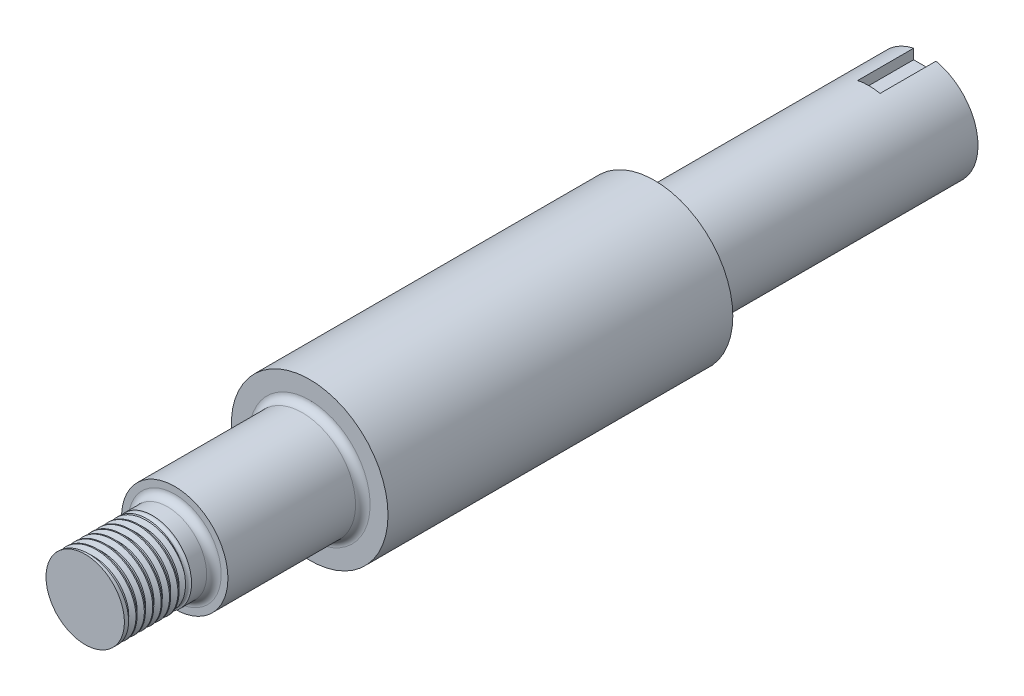
SolidWorks part; units mm, degrees
material "AISI 1020"
ref_plane "Front Plane" through (0, 0, 0) normal (0, 0, 1) x (1, 0, 0)
ref_plane "Top Plane" through (0, 0, 0) normal (0, 1, 0) x (1, 0, 0)
ref_plane "Right Plane" through (0, 0, 0) normal (1, 0, 0) x (0, 0, -1)
sketch "Sketch Spindle Skeleton" plane through (0, 0, 0) normal (1, 0, 0) x (0, 0, -1)
  line L0 (-109.9, -9.5) -> (-134, -9.5)
  line L5 (-1000, 0) -> (49000, 0)
  line L6 (0, -9.5) -> (0, 9.5)
  line L13 (0, 9.5) -> (-48.3, 9.5)
  line L26 (-48.3, 9.5) -> (-48.3, 14)
  line L27 (-48.3, 14) -> (-109.9, 14)
  line L32 (-109.9, 14) -> (-109.9, 9.5)
  line L34 (-150, 7) -> (-150, -7)
  line L36 (-109.9, -9.5) -> (-109.9, -14)
  line L37 (-109.9, -14) -> (-48.3, -14)
  line L38 (-48.3, -14) -> (-48.3, -9.5)
  line L39 (0, -9.5) -> (-48.3, -9.5)
  line L40 (-24.2, 36) -> (-19.2, 36)
  line L41 (-126.5, 22.5) -> (-109.9, 22.5)
  line L42 (-126.5, 22.5) -> (-126.5, -22.5)
  line L43 (-126.5, -22.5) -> (-109.9, -22.5)
  line L44 (-109.9, 22.5) -> (-109.9, -22.5)
  line L45 (-126.5, 22.5) -> (-109.9, -22.5) construction
  line L46 (-126.5, -22.5) -> (-109.9, 22.5) construction
  line L47 (-31.7, 22.5) -> (-48.3, 22.5)
  line L48 (-31.7, 22.5) -> (-31.7, -22.5)
  line L49 (-31.7, -22.5) -> (-48.3, -22.5)
  line L50 (-48.3, 22.5) -> (-48.3, -22.5)
  line L51 (-31.7, 22.5) -> (-48.3, -22.5) construction
  line L52 (-31.7, -22.5) -> (-48.3, 22.5) construction
  line L59 (-19.2, 36) -> (-19.2, -36)
  line L60 (-19.2, -36) -> (-24.2, -36)
  line L61 (-24.2, -22.5) -> (-29.2, -22.5)
  line L62 (-29.2, -22.5) -> (-29.2, -17.5)
  line L63 (-29.2, -17.5) -> (-24.2, -17.5)
  line L64 (-24.2, -17.5) -> (-24.2, 17.5)
  line L65 (-24.2, 17.5) -> (-29.2, 17.5)
  line L66 (-29.2, 17.5) -> (-29.2, 22.5)
  line L67 (-29.2, 22.5) -> (-24.2, 22.5)
  line L68 (-24.2, 22.5) -> (-24.2, 36)
  line L69 (-24.2, -22.5) -> (-24.2, -36)
  line L71 (-131.5, 36) -> (-25.2, 36)
  line L72 (-131.5, 36) -> (-131.5, -36)
  line L73 (-131.5, -36) -> (-25.2, -36)
  line L74 (-25.2, 36) -> (-25.2, -36)
  line L75 (-131.5, 36) -> (-25.2, -36) construction
  line L76 (-131.5, -36) -> (-25.2, 36) construction
  line L77 (-134, -9.5) -> (-134, -7)
  line L78 (-134, -7) -> (-150, -7)
  line L79 (-109.9, 9.5) -> (-134, 9.5)
  line L80 (-134, 7) -> (-150, 7)
  line L81 (-134, 9.5) -> (-134, 7)
  line L82 (-121.95, 9.5) -> (-121.95, -9.5) construction
  line L83 (-24.15, 9.5) -> (-24.15, -9.5) construction
  point P3 (0, 0)
  point P18 (-118.2, 0)
  point P24 (-40, 0)
  point P29 (-78.35, 0)
  point P48 (-19.2, 29.25)
revolve "Revolve Spindle" add sketch "Sketch Spindle Skeleton" angle 360 about L5 region at (0, 7, 79.1) region at (0, 4.75, 118.2) region at (0, 4.75, 129) region at (0, 4.75, 40) region at (0, 3.7187, 140.3817) region at (0, 4.75, 28.45) region at (0, 4.75, 24.7) region at (0, 4.75, 21.7) region at (0, 4.75, 9.6)
fillet "Bearing Rest Fillet 0.13cm " radius 1.3 3 edges at (9.5, 0, 48.3) (9.5, 0, 109.9) (7, 0, 134)
thread "Chuck Thread" pitch 1.5 method cut profile "Thread Profile2" start angle 0, offset 0, length 10, pitch 1.5, diameter 14
ref_plane "Plane2" through (-7, 0, 150) normal (0, -1, 0) x (-1, 0, 0)
sketch "Thread Profile2" plane through (-7, 0, 150) normal (0, -1, 0) x (-1, 0, 0)
  line L0 (0, 0) -> (0, 1.5) construction
  line L11 (0, 0) -> (0, 1.3125)
  line L12 (0, 1.3125) -> (-0.8119, 0.8437)
  line L13 (-0.8119, 0.8437) -> (-0.8119, 0.4687)
  line L15 (-0.8119, 0.4687) -> (0, 0)
  line L17 (-0.8119, 0.6562) -> (0, 0.6562) construction
  point P2 (0, 0)
  dimension "Pitch" = 1.5
  dimension "Profile_Angle" = 60
  dimension "Profile_Land" = 0.375
  dimension "Profile_Height" = 0.8119
sketch "Thread Slot Sketch" plane through (0, 0, 0) normal (1, 0, 0) x (0, 0, -1)
  line L0 (-138.6882, -6.0622) -> (-140.0007, -6.0622) construction
  line L1 (-138.6882, -6.0622) -> (-140.0007, -6.0622)
  line L5 (-140.0625, -7) -> (-135.3, -7) construction
  line L6 (-150, 7) -> (-150, -7) construction
  circle A0 centre (-138.5, -7) radius 0.5
  point P4 (-139.1882, -7.7659)
  point P5 (-139.1882, -8.0012)
  point P6 (-137.9483, -7)
  dimension "D1" = 1
  dimension "D2" = 11.5
revolve "Thread Slot" cut sketch "Thread Slot Sketch" angle 360 about L5
sketch "Sketch Key" plane through (0, 0, 0) normal (0, 0, -1) x (-1, 0, 0)
  line L0 (0, 8.5) -> (0, 0) construction
  line L1 (-2, 7.5) -> (2, 7.5)
  line L2 (-2, 7.5) -> (-2, 9.5)
  line L3 (-2, 9.5) -> (2, 9.5)
  line L4 (2, 7.5) -> (2, 9.5)
  line L5 (-2, 7.5) -> (2, 9.5) construction
  line L6 (-2, 9.5) -> (2, 7.5) construction
  circle A1 centre (0, 0) radius 9.5
  circle A2 centre (0, 0) radius 9.5
  point P0 (0, 8.5)
  dimension "D2" = 4
  dimension "D3" = 2
  dimension "D1" = 0
extrude "Key Cut" cut sketch "Sketch Key" against normal blind 10 contours L3 L4 L1 L2
